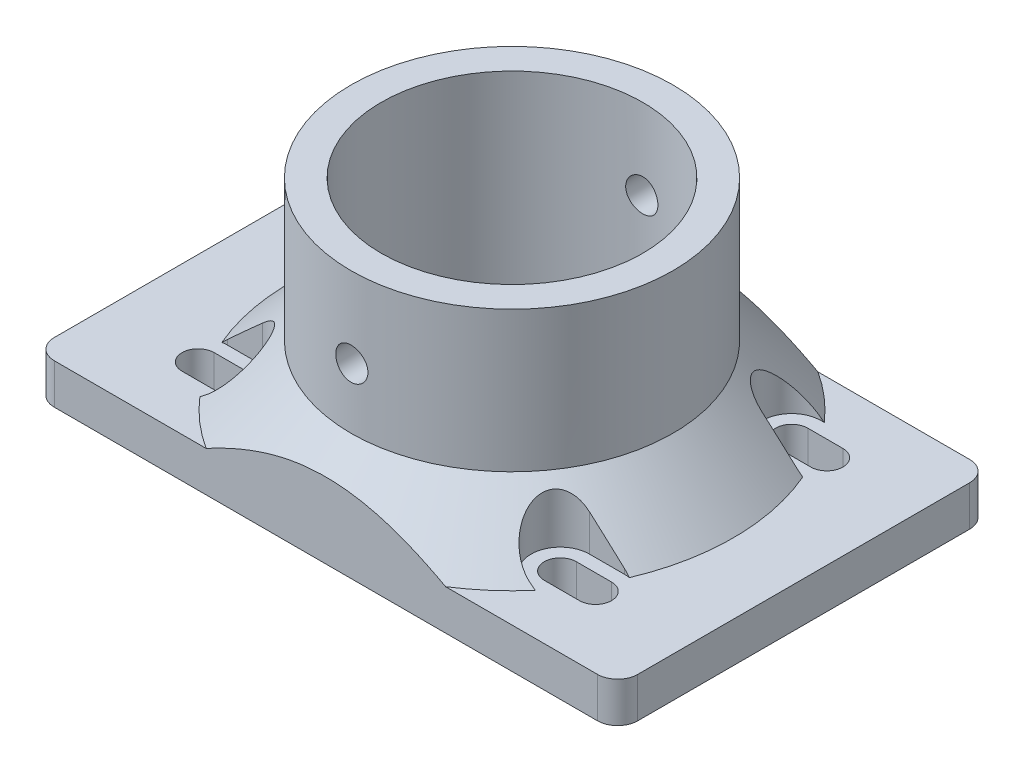
SolidWorks part; units mm, degrees
material "PET"
ref_plane "Спереди" through (0, 0, 0) normal (0, 0, 1) x (1, 0, 0)
ref_plane "Сверху" through (0, 0, 0) normal (0, 1, 0) x (1, 0, 0)
ref_plane "Справа" through (0, 0, 0) normal (1, 0, 0) x (0, 0, -1)
sketch "Эскиз1" plane through (0, 0, 0) normal (0, 1, 0) x (1, 0, 0)
  line L0 (0, 0) -> (-64.6711, 0) construction
  line L1 (27, 18.5) -> (-27, 18.5)
  line L2 (29, 16.5) -> (29, -16.5)
  line L3 (27, -18.5) -> (-27, -18.5)
  line L4 (-29, 16.5) -> (-29, -16.5)
  line L5 (0, 0) -> (0, 30.1257) construction
  line L6 (-19.75, -11.4506) -> (-16.25, -11.4506) construction
  line L7 (-19.75, -9.8506) -> (-16.25, -9.8506)
  line L8 (-19.75, -13.0506) -> (-16.25, -13.0506)
  line L9 (-22.4938, 11.45) -> (-15.3671, 11.45)
  line L10 (18, -9.8506) -> (18, -15.2919)
  line L11 (16.25, -11.4506) -> (19.75, -11.4506) construction
  line L12 (16.25, -9.8506) -> (19.75, -9.8506)
  line L13 (16.25, -13.0506) -> (19.75, -13.0506)
  line L14 (16.25, 11.5494) -> (19.75, 11.5494) construction
  line L15 (16.25, 13.1494) -> (19.75, 13.1494)
  line L16 (16.25, 9.9494) -> (19.75, 9.9494)
  line L17 (-19.75, 11.5494) -> (-16.25, 11.5494) construction
  line L18 (-19.75, 13.1494) -> (-16.25, 13.1494)
  line L19 (-19.75, 9.9494) -> (-16.25, 9.9494)
  arc A4 (29, -16.5) -> (27, -18.5) centre (27, -16.5) cw
  arc A5 (27, 18.5) -> (29, 16.5) centre (27, 16.5) cw
  arc A6 (-27, 18.5) -> (-29, 16.5) centre (-27, 16.5) ccw
  arc A7 (-29, -16.5) -> (-27, -18.5) centre (-27, -16.5) ccw
  arc A8 (-19.75, -9.8506) -> (-19.75, -13.0506) centre (-19.75, -11.4506) ccw
  arc A9 (-16.25, -13.0506) -> (-16.25, -9.8506) centre (-16.25, -11.4506) ccw
  arc A10 (16.25, -9.8506) -> (16.25, -13.0506) centre (16.25, -11.4506) ccw
  arc A11 (19.75, -13.0506) -> (19.75, -9.8506) centre (19.75, -11.4506) ccw
  arc A12 (16.25, 13.1494) -> (16.25, 9.9494) centre (16.25, 11.5494) ccw
  arc A13 (19.75, 9.9494) -> (19.75, 13.1494) centre (19.75, 11.5494) ccw
  arc A14 (-19.75, 13.1494) -> (-19.75, 9.9494) centre (-19.75, 11.5494) ccw
  arc A15 (-16.25, 9.9494) -> (-16.25, 13.1494) centre (-16.25, 11.5494) ccw
  point P0 (0, 0)
  point P19 (-18, -11.4506)
  point P23 (29, -18.5)
  point P26 (29, 18.5)
  point P31 (-29, -18.5)
  point P36 (18, -11.4506)
  point P43 (18, 11.5494)
  point P50 (-18, 11.5494)
  dimension "D3" = 3.2
  dimension "D4" = 7.05
  dimension "D7" = 2
  dimension "D1" = 58
  dimension "D2" = 37
  dimension "D5" = 11
  dimension "D6" = 2
  dimension "D8" = 3.5
  dimension "D9" = 2
extrude "Бобышка-Вытянуть1" add sketch "Эскиз1" along normal blind 4 contours L4 A7 L3 A4 L2 A5 L1 A6 A15 L19 A14 L18 A13 L16 A12 L15 A11 L13 A10 L12 A9 L8 A8 L7 region at (0, 0, 0.0018)
sketch "Эскиз2" plane through (0, 4, 0) normal (0, 1, 0) x (1, 0, 0)
  circle A0 centre (0, 0) radius 13
  circle A1 centre (0, 0) radius 16
  dimension "D1" = 26
  dimension "D2" = 32
extrude "Бобышка-Вытянуть2" add sketch "Эскиз2" along normal blind 20
sketch "Эскиз3" plane through (0, 0, 0) normal (0, 0, 1) x (1, 0, 0)
  circle A0 centre (0, 16) radius 1.6
  dimension "D2" = 3.2
  dimension "D1" = 16
extrude "Вырез-Вытянуть1" cut sketch "Эскиз3" against normal through all both and the other way through all
chamfer "Фаска1" distance 6 angle 45 1 edges at (0, 4, 16)
sketch "Эскиз4" plane through (0, 4, 0) normal (0, 1, 0) x (1, 0, 0)
  line L0 (-19.75, 11.5494) -> (-16.25, 11.5494) construction
  line L1 (-19.75, 14.4554) -> (-16.25, 14.4554)
  line L2 (-19.75, 8.6435) -> (-16.25, 8.6435)
  line L3 (16.25, 11.5494) -> (19.75, 11.5494) construction
  line L4 (16.25, 14.4554) -> (19.75, 14.4554)
  line L5 (16.25, 8.6435) -> (19.75, 8.6435)
  line L6 (16.25, -11.4506) -> (19.75, -11.4506) construction
  line L7 (16.25, -8.5446) -> (19.75, -8.5446)
  line L8 (16.25, -14.3565) -> (19.75, -14.3565)
  line L9 (-19.75, -11.4506) -> (-16.25, -11.4506) construction
  line L10 (-19.75, -8.5446) -> (-16.25, -8.5446)
  line L11 (-19.75, -14.3565) -> (-16.25, -14.3565)
  arc A0 (-19.75, 14.4554) -> (-19.75, 8.6435) centre (-19.75, 11.5494) ccw
  arc A1 (-16.25, 8.6435) -> (-16.25, 14.4554) centre (-16.25, 11.5494) ccw
  arc A2 (16.25, 14.4554) -> (16.25, 8.6435) centre (16.25, 11.5494) ccw
  arc A3 (19.75, 8.6435) -> (19.75, 14.4554) centre (19.75, 11.5494) ccw
  arc A4 (16.25, -8.5446) -> (16.25, -14.3565) centre (16.25, -11.4506) ccw
  arc A5 (19.75, -14.3565) -> (19.75, -8.5446) centre (19.75, -11.4506) ccw
  arc A6 (-19.75, -8.5446) -> (-19.75, -14.3565) centre (-19.75, -11.4506) ccw
  arc A7 (-16.25, -14.3565) -> (-16.25, -8.5446) centre (-16.25, -11.4506) ccw
  point P6 (-18, 11.5494)
  point P16 (18, 11.5494)
  point P23 (18, -11.4506)
  point P30 (-18, -11.4506)
  dimension "D1" = 2
  dimension "D2" = 2
extrude "Вырез-Вытянуть2" cut sketch "Эскиз4" along normal blind 20
